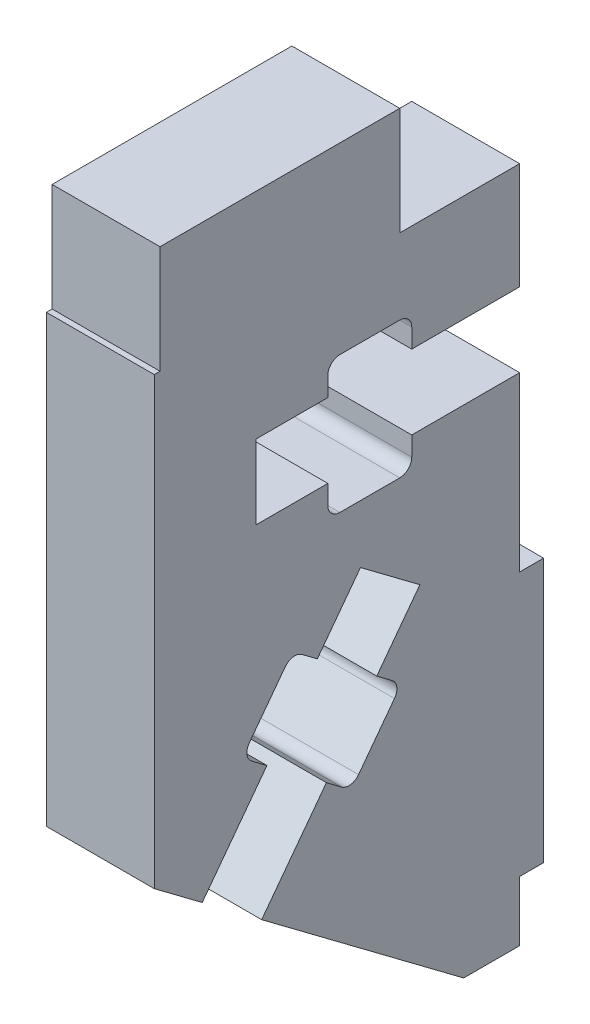
SolidWorks part; units mm, degrees
ref_plane "Front Plane" through (0, 0, 0) normal (0, 0, 1) x (1, 0, 0)
ref_plane "Top Plane" through (0, 0, 0) normal (0, 1, 0) x (1, 0, 0)
ref_plane "Right Plane" through (0, 0, 0) normal (1, 0, 0) x (0, 0, -1)
sketch "Sketch1" plane through (0, 0, 0) normal (1, 0, 0) x (0, 0, -1)
  line L0 (0, 0) -> (0, -30)
  line L1 (0, -30) -> (-40, 0)
  line L2 (-40, 0) -> (0, 0)
  dimension "D1" = 40
  dimension "D2" = 30
extrude "Boss-Extrude1" add sketch "Sketch1" along normal blind 4.5
sketch "Sketch2" plane through (4.5, 0, 0) normal (1, 0, 0) x (0, 0, -1)
  line L0 (0, -25.75) -> (1, -25.75)
  line L1 (0, -30) -> (0, 0) construction
  line L2 (1, -25.75) -> (1, -14.75)
  line L3 (1, -14.75) -> (0, -14.75)
  line L4 (0, -14.75) -> (0, -25.75)
  line L5 (1, -20.25) -> (0, -20.25) construction
  line L6 (0, -14.75) -> (4.5, -14.75) construction
  line L7 (0, -25.75) -> (4.5, -25.75) construction
  dimension "D1" = 0
  dimension "D2" = 1
  dimension "D3" = 0
extrude "Boss-Extrude2" add sketch "Sketch2" against normal through all
sketch "Sketch3" plane through (4.5, 0, 0) normal (1, 0, 0) x (0, 0, -1)
  line L0 (0, -6) -> (-11, -6) construction
  line L1 (0, -14.75) -> (0, 0) construction
  line L2 (-11, -7.55) -> (-11, -4.45) construction
  line L3 (-11, -4.45) -> (0, -4.45) construction
  line L4 (0, -4.45) -> (-4.5, -4.45)
  line L5 (-4.5, -4.45) -> (-4.5, -3.65)
  line L6 (-5, -3.15) -> (-7.5, -3.15)
  line L7 (-8, -3.65) -> (-8, -4.45)
  line L8 (-8, -4.45) -> (-11, -4.45)
  line L9 (-11, -4.45) -> (-11, -7.55)
  line L10 (0, -4.45) -> (0, -7.55)
  line L12 (-11, -7.55) -> (0, -7.55) construction
  line L13 (-8, -7.55) -> (-11, -7.55)
  line L14 (-8, -8.35) -> (-8, -7.55)
  line L15 (-5, -8.85) -> (-7.5, -8.85)
  line L16 (-4.5, -7.55) -> (-4.5, -8.35)
  line L17 (0, -7.55) -> (-4.5, -7.55)
  arc A0 (-4.5, -3.65) -> (-5, -3.15) centre (-5, -3.65) ccw
  arc A1 (-7.5, -3.15) -> (-8, -3.65) centre (-7.5, -3.65) ccw
  arc A2 (-7.5, -8.85) -> (-8, -8.35) centre (-7.5, -8.35) cw
  arc A3 (-4.5, -8.35) -> (-5, -8.85) centre (-5, -8.35) cw
  point P15 (-4.5, -3.15)
  point P18 (-8, -3.15)
  point P29 (-8, -8.85)
  point P30 (-4.5, -8.85)
  dimension "D7" = 0.5
  dimension "D1" = 11
  dimension "D2" = 1.55
  dimension "D3" = 3.5
  dimension "D4" = 2.85
  dimension "D5" = 8
  dimension "D6" = 6
extrude "Cut-Extrude1" cut sketch "Sketch3" against normal through all
sketch "Sketch4" plane through (4.5, 0, 0) normal (1, 0, 0) x (0, 0, -1)
  line L0 (-13.24, -20.07) -> (-6.64, -11.27) construction
  line L1 (-40, 0) -> (0, -30) construction
  line L2 (-6.64, -11.27) -> (-4.16, -13.13) construction
  line L3 (-5.4, -12.2) -> (-12, -21) construction
  line L4 (-10.76, -21.93) -> (-13.24, -20.07)
  line L5 (-13.24, -20.07) -> (-10.54, -16.47)
  line L6 (-10.54, -16.47) -> (-11.18, -15.99)
  line L7 (-11.28, -15.29) -> (-9.78, -13.29)
  line L8 (-9.08, -13.19) -> (-8.44, -13.67)
  line L9 (-8.44, -13.67) -> (-6.64, -11.27)
  line L10 (-6.64, -11.27) -> (-4.16, -13.13)
  line L11 (0, 0) -> (-40, 0) construction
  line L12 (-10.76, -21.93) -> (-4.16, -13.13) construction
  line L13 (-5.96, -15.53) -> (-4.16, -13.13)
  line L14 (-5.32, -16.01) -> (-5.96, -15.53)
  line L15 (-6.72, -18.71) -> (-5.22, -16.71)
  line L16 (-8.06, -18.33) -> (-7.42, -18.81)
  line L17 (-10.76, -21.93) -> (-8.06, -18.33)
  arc A0 (-11.18, -15.99) -> (-11.28, -15.29) centre (-10.88, -15.59) cw
  arc A1 (-9.78, -13.29) -> (-9.08, -13.19) centre (-9.38, -13.59) cw
  arc A2 (-5.22, -16.71) -> (-5.32, -16.01) centre (-5.62, -16.41) ccw
  arc A3 (-7.42, -18.81) -> (-6.72, -18.71) centre (-7.12, -18.41) ccw
  point P14 (-11.58, -15.69)
  point P17 (-9.48, -12.89)
  point P28 (-4.92, -16.31)
  point P29 (-7.02, -19.11)
  dimension "D7" = 0.5
  dimension "D1" = 11
  dimension "D2" = 1.55
  dimension "D3" = 3.5
  dimension "D4" = 2.85
  dimension "D5" = 8
  dimension "D6" = 21
extrude "Cut-Extrude2" cut sketch "Sketch4" against normal through all
sketch "Sketch5" plane through (4.5, 0, 0) normal (1, 0, 0) x (0, 0, -1)
  line L0 (-15.24, -18.57) -> (-15.24, 0)
  line L1 (-40, 0) -> (-13.24, -20.07) construction
  line L2 (0, 0) -> (-40, 0) construction
  line L3 (-15.24, 0) -> (-40, 0)
  line L4 (-40, 0) -> (-15.24, -18.57)
  dimension "D1" = 2
extrude "Cut-Extrude3" cut sketch "Sketch5" against normal through all
sketch "Sketch6" plane through (0, 0, 11) normal (0, 0, -1) x (-1, 0, 0)
  line L0 (-2.25, -4.45) -> (-2.25, -7.55) construction
  line L1 (0, -4.45) -> (-4.5, -4.45) construction
  line L2 (0, -7.55) -> (-4.5, -7.55) construction
  circle A0 centre (-2.25, -6) radius 1.5
  dimension "D1" = 3
sketch "Sketch7" plane through (0, -10.4, 7.8) normal (0, -0.8, 0.6) x (1, 0, 0)
  line L0 (2.25, -1.45) -> (2.25, -4.55) construction
  line L1 (0, -1.45) -> (4.5, -1.45) construction
  line L2 (0, -4.55) -> (4.5, -4.55) construction
  circle A0 centre (2.25, -3) radius 1.55
sketch "Sketch8" plane through (4.5, 0, 0) normal (1, 0, 0) x (0, 0, -1)
  line L0 (-10, 4.5) -> (-10, 0) construction
  line L1 (-15, 0) -> (-5, 0)
  line L2 (-15, 0) -> (-15, 4.5)
  line L3 (-15, 4.5) -> (-5, 4.5)
  line L4 (-5, 0) -> (-5, 4.5)
  line L5 (0, 0) -> (-15.24, 0) construction
  dimension "D1" = 10
  dimension "D2" = 4.5
  dimension "D3" = 10
extrude "Boss-Extrude3" add sketch "Sketch8" against normal through all
sketch "Sketch10" plane through (4.5, 0, 0) normal (1, 0, 0) x (0, 0, -1)
  line L0 (0, -28.25) -> (-2.3333, -28.25)
  line L1 (0, -30) -> (0, -25.75) construction
  line L2 (-10.76, -21.93) -> (0, -30) construction
  line L3 (-2.3333, -28.25) -> (0, -30)
  line L4 (0, -30) -> (0, -28.25)
  dimension "D1" = 0
extrude "Cut-Extrude4" cut sketch "Sketch10" against normal through all contours L0 L3 L4
equation "\"X-ROD-SPACING\"=45"
equation "\"Y-ROD-SPACING\"=75"
equation "\"Z-ROD-SPACING\"=17.5"
equation "\"Y-BED-OFFSET\"=2"
equation "\"Y-BED-ROD-INSET\"=3.5"
equation "\"Y-BED-SCREW-SPACING\"=209"
equation "\"Y-BED-SCREW-CUTOUT-SLOT-HEIGHT\"=2"
equation "\"T-SLOT-NUT-FILLET-RADIUS\"=0.5"
equation "\"T-SLOT-SCREW-SHAFT-RADIUS\"=1.55"
equation "\"T-SLOT-SCREW-SHAFT-CUTOUT-LENGTH\"=11"
equation "\"T-SLOT-NUT-DEPTH\"=3.5"
equation "\"T-SLOT-NUT-WIDTH\"=2.85"
equation "\"T-SLOT-NUT-END-DISTANCE\"=8"
equation "\"ACRYLIC-THICKNESS\"=10"
equation "\"ACRYLIC-THICKNESS2\"=4.5"
equation "\"ACRYLIC-TAB-CUTOUT-SIZE\"=\"ACRYLIC-THICKNESS\"+\"ACRYLIC-TAB-TOLERANCE\"*2"
equation "\"ACRYLIC-TAB-TOLERANCE\"=-.05"
equation "\"ACRYLIC-TAB-WIDTH\"=\"ACRYLIC-THICKNESS\""
equation "\"ACRYLIC-M3-HOLE\"=2.9"
equation "\"SMOOTHROD-CAP-SCREW-DISTANCE\"=20"
equation "\"FRAME-WIDTH-INNER\"=370"
equation "\"NEMA17-HOLE-SPACING\"=31"
equation "\"NEMA17-CENTRAL-CUTOUT\"=22.5"
equation "\"Z-BRACKET-REACH\"=55"
equation "\"Z-ROD-INSET\"=13.5"
equation "\"TOP-BRACKET-SPACING\"=40"
equation "\"SMOOTHROD-X-LENGTH\"=350"
equation "\"SMOOTHROD-Y-LENGTH\"=350"
equation "\"SMOOTHROD-Z-LENGTH\"=350"
equation "\"SMOOTHROD-TIGHTENING-HEADROOM\"=.25"
equation "\"LEADSCREW-Z-LENGTH\"=300"
equation "\"SCREW-LENGTH-FRAME\"=\"ACRYLIC-THICKNESS\" + 10"
equation "\"SCREW-LENGTH-MOTOR\"=\"ACRYLIC-THICKNESS\" + 5"
equation "\"SCREW-LENGTH-EXTRUDER\"=28"
equation "\"SCREW-HEAD-RADIUS\"=6"
equation "\"PRINTED-M3-HOLE\"=3.5"
equation "\"PRINTED-X-SMOOTHROD-DIAMETER\"=9.0"
equation "\"PRINTED-X-SMOOTHROD-CUTOUT\"=10"
equation "\"PRINTED-X-BASE-HEIGHT\"=10"
equation "\"PRINTED-LM8UU-CUTOUT-SIZE\"=15.5"
equation "\"PRINTED-LM8UU-CUTOUT-LENGTH\"=24.5"
equation "\"PRINTED-X-IDLER-HEIGHT\"=16"
equation "\"PRINTED-M3-NUT-AF\"=6.25"
equation "\"PSU-MOUNTING-WIDTH\"=95"
equation "\"PSU-MOUNTING-HEIGHT\"=177"
equation "\"Y-BELT-TO-ROD-DISTANCE\"=20"
equation "\"SPOOL-HOLDER-ROD-SPACING\"=150"
equation "\"ACRYLIC-X-CARRIAGE-WIDTH\"=55"
equation "\"ACRYLIC-X-CARRIAGE-HEIGHT\"=75"
equation "\"ACRYLIC-X-CARRIAGE-LM8UU-CUTOUT-WIDTH\"=24.25"
equation "\"ACRYLIC-X-CARRIAGE-LM8UU-CUTOUT-HEIGHT\"=11.0"
equation "\"ACRYLIC-X-CARRIAGE-SCREW-SPACING-X\"=15"
equation "\"ACRYLIC-X-CARRIAGE-SCREW-SPACING-Y\"=33"
equation "\"ACRYLIC-X-CARRIAGE-CENTER-TAB-SPACING\"=14"
equation "\"ACRYLIC-X-CARRIAGE-EXTRUDER-OFFSET\"=26"
equation "\"ACRYLIC-X-CARRIAGE-EXTRUDER-ANGLE\"=90"
equation "\"ACRYLIC-X-CARRIAGE-EXTRUDER-SHELF-DEPTH\"=\"ACRYLIC-X-CARRIAGE-EXTRUDER-OFFSET\" + 28"
equation "\"ACRYLIC-X-CARRIAGE-EXTRUDER-BRACE-SPACING\"=23"
equation "\"ACRYLIC-X-CARRIAGE-EXTRUDER-BRACE-TAB-OFFSET\"=20"
equation "\"ACRYLIC-X-CARRIAGE-EXTRUDER-BRACE-HEIGHT\"=35"
equation "\"ACRYLIC-X-CARRIAGE-EXTRUDER-BRACE-SCREW-SPACING\"=22"
equation "\"ACRYLIC-X-CARRIAGE-DUAL-WIDTH-MULTIPLIER\"=1.65"
equation "\"ACRYLIC-X-CARRIAGE-DUAL-HOTEND-SPACING\"=42"
equation "\"ACRYLIC-X-CARRIAGE-DUAL-WIDTH\"=75"
equation "\"ACRYLIC-X-CARRIAGE-DUAL-FAN-OFFSET\"=52"
equation "\"ACRYLIC-X-CARRIAGE-DUAL-FAN-HEIGHT\"=20"
equation "\"ACRYLIC-X-CARRIAGE-DUAL-HOTEND-SEPARATION\"=36"
equation "\"ACRYLIC-X-CARRIAGE-DUAL-MOUNT-PLATE-DEPTH\"=75"
equation "\"ACRYLIC-X-CARRIAGE-DUAL-MOUNT-BRACE-WIDTH\"=33"
equation "\"ACRYLIC-X-CARRIAGE-DUAL-MOUNT-SCREW-WIDTH\"=40"
equation "\"BLOWER-FAN-WIDTH\"=15"
equation "\"D1@Boss-Extrude1\"=\"ACRYLIC-THICKNESS2\""
equation "\"D1@Sketch3\"=\"T-SLOT-SCREW-SHAFT-CUTOUT-LENGTH\""
equation "\"D2@Sketch3\"=\"T-SLOT-SCREW-SHAFT-RADIUS\""
equation "\"D3@Sketch3\"=\"T-SLOT-NUT-DEPTH\""
equation "\"D4@Sketch3\"=\"T-SLOT-NUT-WIDTH\""
equation "\"D5@Sketch3\"=\"T-SLOT-NUT-END-DISTANCE\""
equation "\"D7@Sketch3\"=\"T-SLOT-NUT-FILLET-RADIUS\""
equation "\"D1@Sketch4\"=\"T-SLOT-SCREW-SHAFT-CUTOUT-LENGTH\""
equation "\"D2@Sketch4\"=\"T-SLOT-SCREW-SHAFT-RADIUS\""
equation "\"D3@Sketch4\"=\"T-SLOT-NUT-DEPTH\""
equation "\"D4@Sketch4\"=\"T-SLOT-NUT-WIDTH\""
equation "\"D5@Sketch4\"=\"T-SLOT-NUT-END-DISTANCE\""
equation "\"D7@Sketch4\"=\"T-SLOT-NUT-FILLET-RADIUS\""
equation "\"D1@Sketch8\"=\"ACRYLIC-TAB-WIDTH\""
equation "\"D2@Sketch8\"=\"ACRYLIC-THICKNESS2\""
